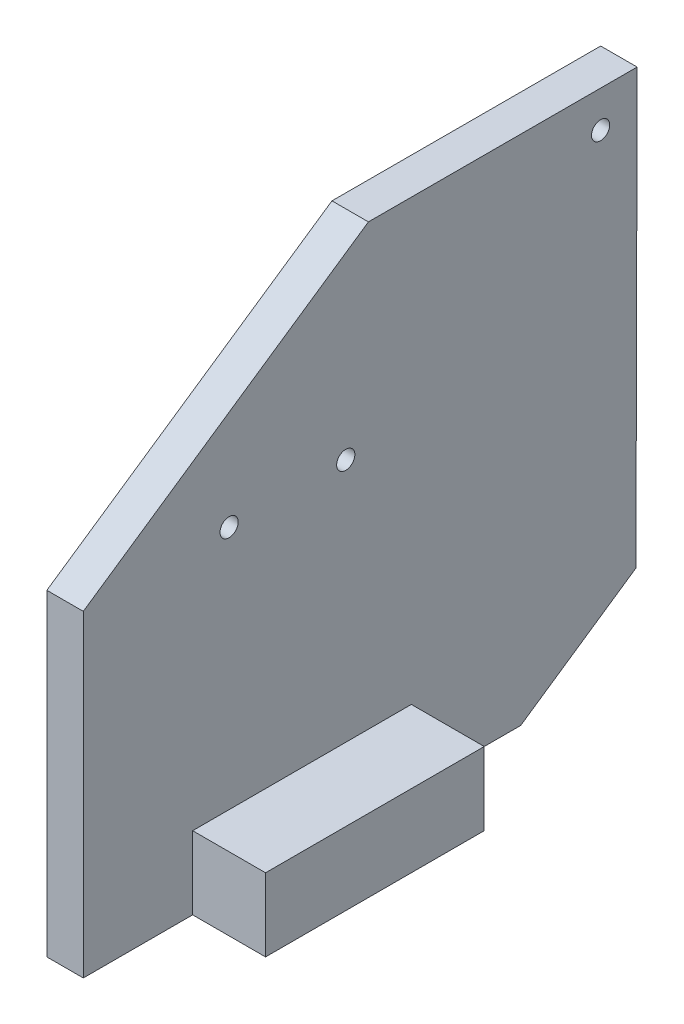
SolidWorks part; units mm, degrees
material "BRASS"
ref_plane "Front Plane" through (0, 0, 0) normal (0, 0, 1) x (1, 0, 0)
ref_plane "Top Plane" through (0, 0, 0) normal (0, 1, 0) x (1, 0, 0)
ref_plane "Right Plane" through (0, 0, 0) normal (1, 0, 0) x (0, 0, -1)
sketch "Sketch2" plane through (0, 0, 0) normal (1, 0, 0) x (0, 0, -1)
  line L6 (0, 0) -> (76.2, 0)
  line L7 (76.2, 0) -> (96.2791, 13.7139)
  line L10 (49.67, 89.2456) -> (0, 55.3212)
  line L12 (49.67, 89.2456) -> (96.4867, 89.1984)
  line L13 (96.4867, 89.1984) -> (96.2791, 13.7139)
  line L15 (0, 55.3212) -> (0, 0)
  line L16 (19.05, 0) -> (19.05, 12.7)
  line L17 (57.15, 0) -> (57.15, 12.7)
  line L18 (44.45, 0) -> (44.45, 12.7) construction
  line L19 (31.75, 0) -> (31.75, 12.7) construction
  line L20 (19.05, 12.7) -> (57.15, 12.7)
  circle A0 centre (25.4, 55.3212) radius 1.5875
  circle A1 centre (90.1192, 82.8548) radius 1.5875
  circle A2 centre (45.72, 55.3212) radius 1.5875
  dimension "D3" = 3.175
  dimension "D1" = 76.2
  dimension "D2" = 25.4
  dimension "D4" = 55.3212
  dimension "D5" = 82.8548
  dimension "D6" = 70.3326
  dimension "D7" = 6.35
  dimension "D8" = 6.35
  dimension "D9" = 12.7
  dimension "D10" = 19.05
  dimension "D11" = 19.05
  dimension "D12" = 12.7
  dimension "D13" = 12.7
  dimension "D14" = 20.32
extrude "Boss-Extrude3" add sketch "Sketch2" against normal blind 6.35 contours L20 L16 L6 L17 | L16 L20 L17 L6 L7 L13 L12 L10 L15 A1 A0 region at (0, 44.0036, -51.7913) region at (0, 6.35, -38.1)
extrude "Boss-Extrude4" add sketch "Sketch2<5>" along normal blind 12.7 contours L20 L16 L6 L17 region at (0, 6.35, -38.1)
sketch "Sketch2<5>" plane through (0, 0, 0) normal (1, 0, 0) x (0, 0, -1) same geometry as "Sketch2"
